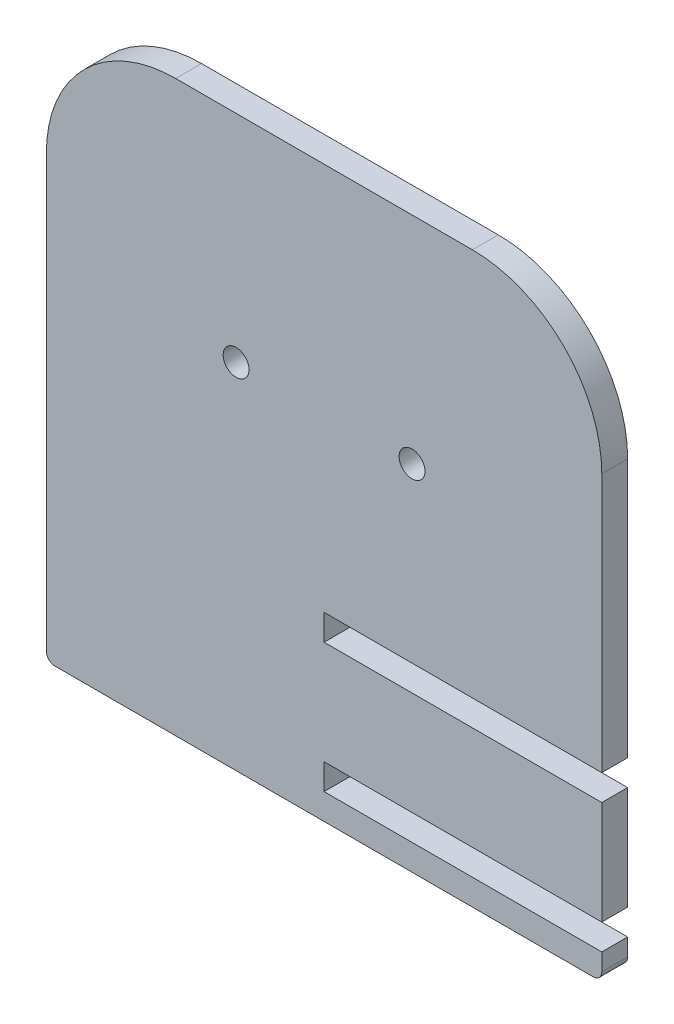
SolidWorks part; units mm, degrees
ref_plane "Front Plane" through (0, 0, 0) normal (0, 0, 1) x (1, 0, 0)
ref_plane "Top Plane" through (0, 0, 0) normal (0, 1, 0) x (1, 0, 0)
ref_plane "Right Plane" through (0, 0, 0) normal (1, 0, 0) x (0, 0, -1)
sketch "Sketch1" plane through (0, 0, 0) normal (0, 0, 1) x (1, 0, 0)
  line L0 (-46.6615, -6.4851) -> (-12.2615, -6.4851)
  line L12 (-61.6615, -21.4851) -> (-61.6615, -51.4851)
  line L17 (2.7385, -66.4851) -> (-29.4615, -66.4851)
  line L19 (2.7385, -69.4851) -> (-29.4615, -69.4851)
  line L20 (-29.4615, -66.4851) -> (-29.4615, -69.4851)
  line L21 (-61.6615, -54.4851) -> (-61.6615, -71.4851)
  line L22 (2.7385, -21.4851) -> (2.7385, -66.4851)
  line L23 (2.7385, -69.4851) -> (2.7385, -71.4851)
  line L24 (-60.6615, -72.4851) -> (1.7385, -72.4851)
  line L25 (-61.6615, -51.4851) -> (-61.6615, -54.4851)
  arc A0 (-12.2615, -6.4851) -> (2.7385, -21.4851) centre (-12.2615, -21.4851) cw
  arc A2 (-46.6615, -6.4851) -> (-61.6615, -21.4851) centre (-46.6615, -21.4851) ccw
  arc A3 (-61.6615, -71.4851) -> (-60.6615, -72.4851) centre (-60.6615, -71.4851) ccw
  arc A4 (1.7385, -72.4851) -> (2.7385, -71.4851) centre (1.7385, -71.4851) ccw
  point P13 (0, 0)
  point P15 (0, 0)
  point P24 (0, 0)
  point P25 (0, 0)
  point P26 (0, 0)
  point P27 (0, 0)
  dimension "D9" = 64.4
  dimension "D4" = 66
  dimension "D2" = 15
  dimension "D3" = 1
  dimension "D6" = 2
  dimension "D10" = 32.2
  dimension "D11" = 3
extrude "Boss-Extrude7" add sketch "Sketch1" along normal blind 3 contours L23 A4 L24 A3 L21 L25 L12 A2 L0 A0 L22 L17 L20 L19
sketch "Sketch3" plane through (0, 0, 3) normal (0, 0, 1) x (1, 0, 0)
  line L0 (-46.6615, -6.4851) -> (-12.2615, -6.4851) construction
  line L1 (2.7385, -21.4851) -> (2.7385, -66.4851) construction
  line L2 (-61.6615, -21.4851) -> (-61.6615, -71.4851) construction
  circle A0 centre (-19.2615, -31.4851) radius 1.5
  circle A1 centre (-39.6615, -31.4851) radius 1.5
  dimension "D1" = 25
  dimension "D3" = 22
  dimension "D2" = 22
  dimension "D4" = 25
extrude "Cut-Extrude1" cut sketch "Sketch3" against normal blind 3
sketch "Sketch4" plane through (0, 0, 3) normal (0, 0, 1) x (1, 0, 0)
  line L0 (-29.4615, -51.4851) -> (2.7385, -51.4851)
  line L1 (-29.4615, -51.4851) -> (-29.4615, -54.4851)
  line L2 (-29.4615, -54.4851) -> (2.7385, -54.4851)
  line L3 (2.7385, -51.4851) -> (2.7385, -54.4851)
  line L4 (-29.4615, -66.4851) -> (-29.4615, -69.4851) construction
  line L5 (2.7385, -21.4851) -> (2.7385, -66.4851) construction
  line L6 (2.7385, -66.4851) -> (-29.4615, -66.4851) construction
  point P4 (-31.4297, -52.4393)
  dimension "D1" = 3
  dimension "D2" = 12
extrude "Cut-Extrude2" cut sketch "Sketch4" against normal blind 3
